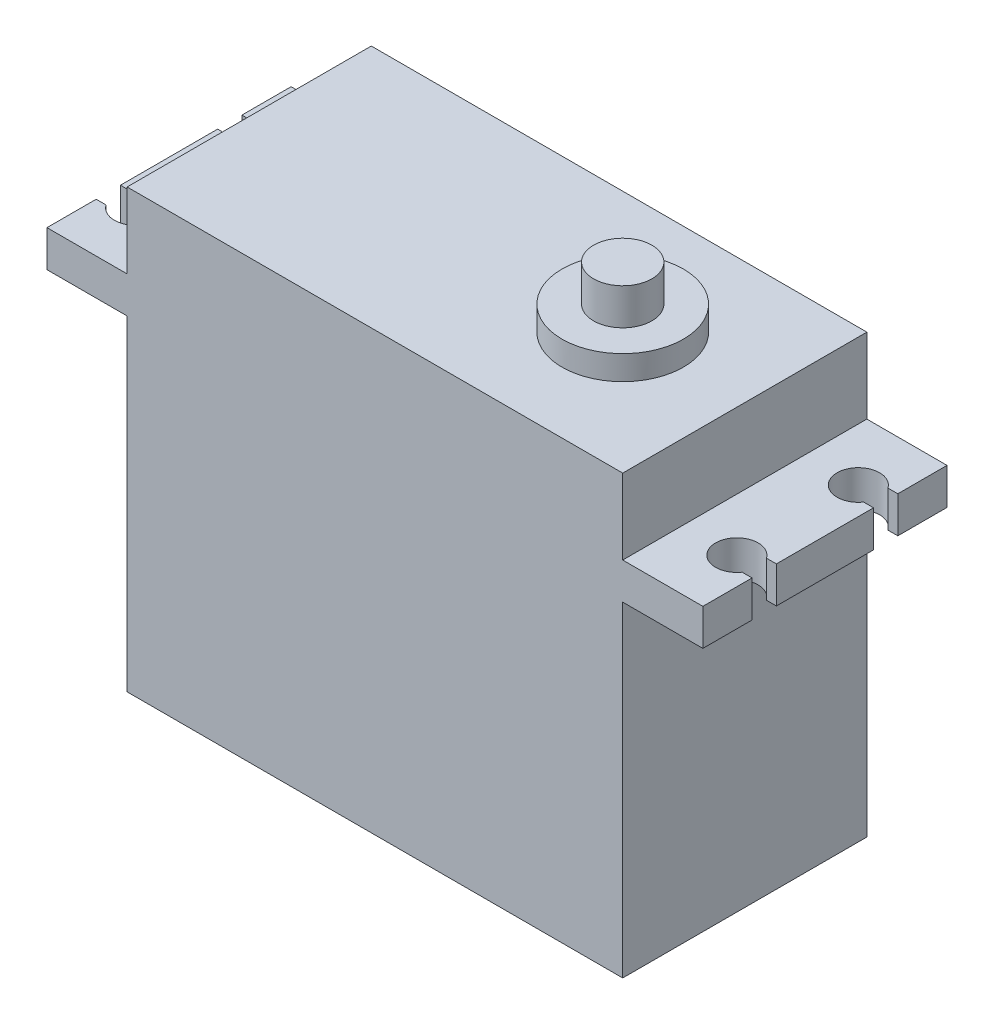
SolidWorks part; units mm, degrees
ref_plane "Front Plane" through (0, 0, 0) normal (0, 0, 1) x (1, 0, 0)
ref_plane "Top Plane" through (0, 0, 0) normal (0, 1, 0) x (1, 0, 0)
ref_plane "Right Plane" through (0, 0, 0) normal (1, 0, 0) x (0, 0, -1)
sketch "Sketch2" plane through (0, 0, 0) normal (0, 1, 0) x (1, 0, 0)
  line L0 (0, 0) -> (0, 10.05) construction
  line L1 (0, 0) -> (10.05, 0) construction
  line L2 (0, 0) -> (0, -10.05) construction
  line L3 (0, 0) -> (-30.75, 0) construction
  line L4 (-35.1, 5) -> (-35.1, -5) construction
  line L5 (-30.75, 10.05) -> (10.05, 10.05)
  line L6 (-30.75, 10.05) -> (-30.75, -10.05)
  line L7 (-30.75, -10.05) -> (10.05, -10.05)
  line L8 (10.05, 10.05) -> (10.05, -10.05)
  line L9 (-30.75, 10.05) -> (-37.35, 10.05) construction
  line L10 (-37.35, 10.05) -> (-37.35, -10.05) construction
  line L11 (-37.35, -10.05) -> (-30.75, -10.05) construction
  line L12 (-10.35, 10.05) -> (-10.35, -10.05) construction
  line L13 (14.4, 5) -> (14.4, -5) construction
  line L14 (-36.85, 5) -> (-37.35, 5) construction
  line L15 (10.05, 10.05) -> (16.65, 10.05) construction
  line L16 (16.65, 10.05) -> (16.65, -10.05) construction
  line L17 (16.65, -10.05) -> (10.05, -10.05) construction
  circle A0 centre (0, 0) radius 2.4
  circle A1 centre (0, 0) radius 10.05 construction
  circle A2 centre (-35.1, 5) radius 1.75
  circle A3 centre (-35.1, -5) radius 1.75
  circle A4 centre (14.4, -5) radius 1.75
  circle A5 centre (14.4, 5) radius 1.75
  circle A6 centre (0, 0) radius 5 construction
  dimension "D1" = 4.8
  dimension "D6" = 3.5
  dimension "D8" = 10
  dimension "D2" = 40.8
  dimension "D3" = 20.1
  dimension "D4" = 10
  dimension "D5" = 49.5
  dimension "D7" = 0.5
sketch "Sketch3" plane through (0, 0, 0) normal (0, 0, 1) x (1, 0, 0)
  line L0 (-30.75, 0) -> (-30.75, 26.8)
  line L1 (-30.75, 26.8) -> (-37.35, 26.8)
  line L2 (-37.35, 26.8) -> (-37.35, 29.8)
  line L3 (-37.35, 29.8) -> (-30.75, 29.8)
  line L4 (-30.75, 29.8) -> (-30.75, 36)
  line L5 (-30.75, 36) -> (10.05, 36)
  line L6 (10.05, 36) -> (10.05, 29.8)
  line L7 (10.05, 29.8) -> (16.65, 29.8)
  line L8 (16.65, 29.8) -> (16.65, 26.8)
  line L9 (16.65, 26.8) -> (10.05, 26.8)
  line L10 (10.05, 26.8) -> (10.05, 0)
  line L11 (10.05, 0) -> (-30.75, 0)
  line L12 (-10.35, 0) -> (-10.35, 36) construction
  line L13 (2.4, 0) -> (2.4, 41) construction
  line L14 (2.4, 0) -> (-2.4, 0) construction
  line L15 (2.4, 41) -> (-2.4, 41) construction
  line L16 (-2.4, 41) -> (-2.4, 0) construction
  line L17 (10.05, 0) -> (-10.05, 0) construction
  line L18 (-5, 38) -> (5, 38) construction
  line L19 (-5, 0) -> (-5, 38) construction
  line L20 (5, 38) -> (5, 0) construction
  dimension "D1" = 26.8
  dimension "D2" = 3
  dimension "D3" = 3
  dimension "D4" = 38
  dimension "D5" = 2
extrude "Boss-Extrude1" add sketch "Sketch3" along normal up to vertex (10.05 mm away) from vertex up to point (-30.75, 0, 10.05) starting at point (-30.75, 0, -10.05)
sketch "Sketch4" plane through (0, 29.8, 0) normal (0, 1, 0) x (1, 0, 0)
  line L0 (-10.35, 10.05) -> (-10.35, -10.05) construction
  line L1 (-10.35, 10.05) -> (-10.35, -10.05) construction
  line L2 (-37.35, 10.05) -> (-37.35, -10.05) construction
  line L4 (-37.35, 6) -> (-37.35, 4)
  line L5 (16.65, -6) -> (15.8361, -6)
  line L6 (-10.35, 0) -> (-37.35, 0) construction
  line L7 (-37.35, 4) -> (-36.5361, 4)
  line L8 (-37.35, 6) -> (-36.5361, 6)
  line L9 (-35.1, 5) -> (-37.35, 5) construction
  line L10 (-37.35, -4) -> (-37.35, -6)
  line L11 (-37.35, -4) -> (-36.5361, -4)
  line L12 (-37.35, -6) -> (-36.5361, -6)
  line L13 (16.65, -4) -> (16.65, -6)
  line L14 (16.65, -4) -> (15.8361, -4)
  line L15 (16.65, 4) -> (15.8361, 4)
  line L16 (16.65, 6) -> (16.65, 4)
  line L17 (16.65, 6) -> (15.8361, 6)
  circle A0 centre (-35.1, -5) radius 1.75 construction
  circle A1 centre (-35.1, 5) radius 1.75 construction
  circle A2 centre (14.4, 5) radius 1.75 construction
  circle A3 centre (14.4, -5) radius 1.75 construction
  arc A4 (-36.5361, -6) -> (-36.5361, -4) centre (-35.1, -5) ccw
  arc A5 (-36.5361, 4) -> (-36.5361, 6) centre (-35.1, 5) ccw
  arc A6 (15.8361, 6) -> (15.8361, 4) centre (14.4, 5) ccw
  arc A7 (15.8361, -4) -> (15.8361, -6) centre (14.4, -5) ccw
  dimension "D1" = 2
extrude "Cut-Extrude1" cut sketch "Sketch4" against normal through all
sketch "Sketch5" plane through (0, 36, 0) normal (0, 1, 0) x (1, 0, 0)
  circle A0 centre (0, 0) radius 5 construction
  circle A1 centre (0, 0) radius 5
extrude "Boss-Extrude2" add sketch "Sketch5" along normal up to vertex (2 mm away) up to point (-5, 38, 0)
sketch "Sketch6" plane through (0, 38, 0) normal (0, 1, 0) x (1, 0, 0)
  circle A0 centre (0, 0) radius 2.4 construction
  circle A1 centre (0, 0) radius 2.4
extrude "Boss-Extrude3" add sketch "Sketch6" along normal up to vertex (3 mm away) up to point (-2.4, 41, 0)
